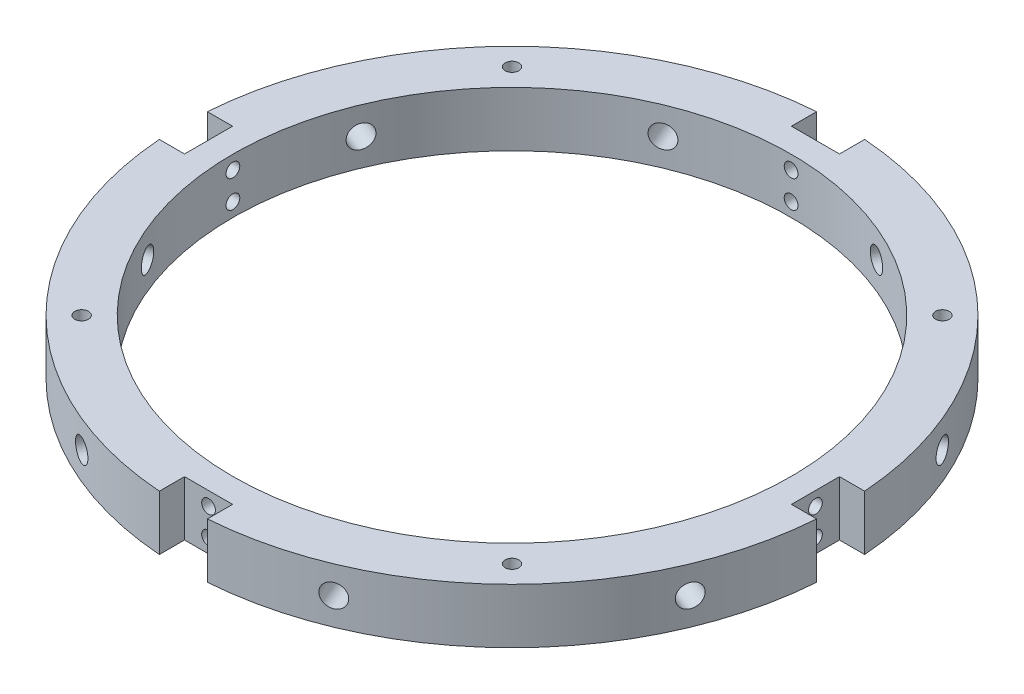
SolidWorks part; units mm, degrees
ref_plane "Front Plane" through (0, 0, 0) normal (0, 0, 1) x (1, 0, 0)
ref_plane "Top Plane" through (0, 0, 0) normal (0, 1, 0) x (1, 0, 0)
ref_plane "Right Plane" through (0, 0, 0) normal (1, 0, 0) x (0, 0, -1)
sketch "Sketch1" plane through (0, 0, 0) normal (0, 1, 0) x (1, 0, 0)
  circle A0 centre (0, 0) radius 72
  circle A1 centre (0, 0) radius 61
  dimension "OuterDiameter" = 144
  dimension "InnerDiameter" = 122
extrude "Boss-Extrude1" add sketch "Sketch1" along normal blind 6 and the other way blind 6
sketch "Sketch13" plane through (0, 6, 0) normal (0, 1, 0) x (1, 0, 0)
  line L0 (0, -87.0356) -> (0, 86.4553) construction
  line L1 (-98.9563, 0) -> (122.4152, 0) construction
  line L2 (0, 0) -> (106.0387, 106.0387) construction
  line L3 (-5.25, -62.375) -> (5.25, -62.375)
  line L4 (-5.25, -62.375) -> (-5.25, -60.7737)
  line L5 (-5.25, -60.7737) -> (5.25, -60.7737)
  line L6 (5.25, -62.375) -> (5.25, -60.7737)
  line L7 (-5.25, -62.375) -> (5.25, -60.7737) construction
  line L8 (-5.25, -60.7737) -> (5.25, -62.375) construction
  line L9 (-5.25, 60.7737) -> (5.25, 60.7737)
  line L10 (5.25, 62.375) -> (5.25, 60.7737)
  line L11 (-5.25, 62.375) -> (5.25, 62.375)
  line L12 (-5.25, 62.375) -> (-5.25, 60.7737)
  line L13 (-60.7737, -5.25) -> (-60.7737, 5.25)
  line L14 (-62.375, 5.25) -> (-60.7737, 5.25)
  line L15 (-62.375, -5.25) -> (-62.375, 5.25)
  line L16 (-62.375, -5.25) -> (-60.7737, -5.25)
  line L17 (62.375, -5.25) -> (60.7737, -5.25)
  line L18 (62.375, -5.25) -> (62.375, 5.25)
  line L19 (62.375, 5.25) -> (60.7737, 5.25)
  line L20 (60.7737, -5.25) -> (60.7737, 5.25)
  circle A0 centre (0, 0) radius 61 construction
  point P7 (0, -61.5743)
  dimension "D1" = 10.5
  dimension "D2" = 62.375
  dimension "D4" = 45
extrude "Boss-Extrude2" [suppressed] add sketch "Sketch13" against normal blind 12
sketch "Sketch5" plane through (0, 6, 0) normal (0, 1, 0) x (1, 0, 0)
  line L0 (0, 0) -> (53.7588, 53.7588) construction
  line L1 (0, 0) -> (47.0226, 47.0226) construction
  line L2 (-121.3123, 0) -> (150.1577, 0) construction
  circle A0 centre (47.0226, 47.0226) radius 1.5
  circle A1 centre (47.0226, -47.0226) radius 1.5
  circle A2 centre (-47.0226, -47.0226) radius 1.5
  circle A3 centre (-47.0226, 47.0226) radius 1.5
  dimension "MountingBoltDiameter" = 3
  dimension "D3" = 45
  dimension "D2" = 66.5
  dimension "D1" = 4
extrude "Cut-Extrude3" cut sketch "Sketch5" against normal through all
sketch "Sketch6" plane through (0, 6, 0) normal (0, 1, 0) x (1, 0, 0)
  line L0 (0, -83.4209) -> (0, 77.0416) construction
  line L1 (-88.8703, 0) -> (103.6253, 0) construction
  line L2 (-5.25, -66.3083) -> (5.25, -66.3083)
  line L4 (-5.25, 71.8083) -> (-5.25, 66.3083)
  line L5 (-5.25, 66.3083) -> (5.25, 66.3083)
  line L6 (5.25, 71.8083) -> (5.25, 66.3083)
  line L7 (-5.25, 71.8083) -> (5.25, 66.3083) construction
  line L8 (-5.25, 66.3083) -> (5.25, 71.8083) construction
  line L9 (5.25, -71.8083) -> (5.25, -66.3083)
  line L11 (-5.25, -71.8083) -> (-5.25, -66.3083)
  line L12 (0, 0) -> (60.635, 60.635) construction
  line L13 (66.3083, -5.25) -> (66.3083, 5.25)
  line L14 (71.8083, 5.25) -> (66.3083, 5.25)
  line L16 (71.8083, -5.25) -> (66.3083, -5.25)
  line L17 (-71.8083, -5.25) -> (-66.3083, -5.25)
  line L19 (-71.8083, 5.25) -> (-66.3083, 5.25)
  line L20 (-66.3083, -5.25) -> (-66.3083, 5.25)
  line L21 (71.8083, 5.25) -> (77.3083, 5.25)
  line L23 (-5.25, 71.8083) -> (-5.25, 77.3083)
  line L24 (-5.25, 77.3083) -> (5.25, 77.3083)
  line L25 (5.25, 71.8083) -> (5.25, 77.3083)
  line L27 (71.8083, -5.25) -> (77.3083, -5.25)
  line L28 (77.3083, 5.25) -> (77.3083, -5.25)
  line L29 (5.25, -71.8083) -> (5.25, -77.3083)
  line L31 (-5.25, -71.8083) -> (-5.25, -77.3083)
  line L32 (5.25, -77.3083) -> (-5.25, -77.3083)
  line L33 (-71.8083, -5.25) -> (-77.3083, -5.25)
  line L35 (-71.8083, 5.25) -> (-77.3083, 5.25)
  line L36 (-77.3083, -5.25) -> (-77.3083, 5.25)
  circle A0 centre (0, 0) radius 72 construction
  point P5 (0, 69.0583)
  point P43 (0, 0)
  circle M6 centre (0, 0) radius 72
  dimension "RailWidth" = 10.5
  dimension "D1" = 5.5
  dimension "D2" = 5.5
extrude "Cut-Extrude4" cut sketch "Sketch6" against normal through all contours L25 L24 L23 M6 | L6 L4 L5 | L28 L21 L27 M6 | L16 L14 L13 | L36 L33 L35 M6 | L17 L20 L19 | L32 L29 L31 M6 | L11 L9 L2 region at (0, 6, 69.1225) region at (0, 6, 74.6219) region at (-69.1225, 6, 0) region at (-74.6219, 6, 0) region at (74.6219, 6, 0) region at (69.1225, 6, 0) region at (0, 6, -69.1225) region at (0, 6, -74.6219)
sketch "Sketch12" plane through (0, 0, 66.3083) normal (0, 0, 1) x (1, 0, 0)
  line L0 (0, 14.272) -> (0, -15.4955) construction
  line L1 (-76.0318, 0) -> (77.9048, 0) construction
  circle A8 centre (0, 3) radius 1.5
  circle A9 centre (0, -3) radius 1.5
  dimension "D2" = 3
  dimension "D1" = 3
extrude "Cut-Extrude8" cut sketch "Sketch12" against normal through all
sketch "Sketch14" plane through (0, 6, 0) normal (0, 1, 0) x (1, 0, 0)
  line L0 (0, 0) -> (-136.7554, 0) construction
  line L1 (0, 0) -> (0, 142.5403) construction
  line L2 (0, 0) -> (-49.7797, 120.1788) construction
  line L3 (0, 0) -> (-96.3261, 96.3261) construction
  line L4 (0, 0) -> (-120.1788, 49.7797) construction
  line L5 (0, 0) -> (-49.7797, -120.1788) construction
  line L6 (0, 0) -> (-120.1788, -49.7797) construction
  line L7 (0, 0) -> (49.7797, -120.1788) construction
  line L8 (0, 0) -> (120.1788, -49.7797) construction
  line L9 (0, 0) -> (120.1788, 49.7797) construction
  line L10 (0, 0) -> (49.7797, 120.1788) construction
  dimension "D1" = 22.5
ref_plane "Plane1" through (-49.7797, 6, -120.1788) normal (-0.3827, 0, -0.9239) x (-0.9239, 0, 0.3827)
ref_plane "Plane2" through (-120.1788, 6, -49.7797) normal (-0.9239, 0, -0.3827) x (-0.3827, 0, 0.9239)
ref_plane "Plane3" through (-120.1788, 6, 49.7797) normal (-0.9239, 0, 0.3827) x (0.3827, 0, 0.9239)
ref_plane "Plane4" through (-49.7797, 6, 120.1788) normal (-0.3827, 0, 0.9239) x (0.9239, 0, 0.3827)
sketch "Sketch15" plane through (-49.7797, 6, -120.1788) normal (-0.3827, 0, -0.9239) x (-0.9239, 0, 0.3827)
  line L0 (-120.7735, -6) -> (151.4229, -6) construction
  circle A0 centre (0, -6) radius 2.5
  dimension "D1" = 5
extrude "Cut-Extrude10" cut sketch "Sketch15" against normal through all
cosmetic thread "Cosmetic Thread1" parameters "D2"=6
cosmetic thread "Cosmetic Thread5" parameters "D2"=6
sketch "Sketch16" plane through (-120.1788, 6, -49.7797) normal (-0.9239, 0, -0.3827) x (-0.3827, 0, 0.9239)
  line L0 (-99.0113, -6) -> (114.7123, -6) construction
  circle A0 centre (0, -6) radius 2.5
  dimension "D1" = 5
extrude "Cut-Extrude11" cut sketch "Sketch16" against normal through all
cosmetic thread "Cosmetic Thread2" parameters "D2"=6
cosmetic thread "Cosmetic Thread6" parameters "D2"=6
sketch "Sketch17" plane through (-120.1788, 6, 49.7797) normal (-0.9239, 0, 0.3827) x (0.3827, 0, 0.9239)
  line L0 (-104.6958, -6) -> (121.5008, -6) construction
  circle A0 centre (0, -6) radius 2.5
  dimension "D1" = 5
extrude "Cut-Extrude12" cut sketch "Sketch17" against normal through all
cosmetic thread "Cosmetic Thread3" parameters "D2"=6
cosmetic thread "Cosmetic Thread7" parameters "D2"=6
sketch "Sketch18" plane through (-49.7797, 6, 120.1788) normal (-0.3827, 0, 0.9239) x (0.9239, 0, 0.3827)
  line L0 (-104.7035, -6) -> (121.0277, -6) construction
  circle A0 centre (0, -6) radius 2.5
  dimension "D1" = 5
extrude "Cut-Extrude13" cut sketch "Sketch18" against normal through all
cosmetic thread "Cosmetic Thread4" parameters "D2"=6
cosmetic thread "Cosmetic Thread8" parameters "D2"=6
sketch "Sketch19" plane through (66.3083, 0, 0) normal (1, 0, 0) x (0, 0, -1)
  line L0 (0, 13.2441) -> (0, -16.5234) construction
  line L1 (-73.8627, 0) -> (80.0739, 0) construction
  line L2 (5.25, 6) -> (-5.25, 6) construction
  line L4 (-5.25, -6) -> (-5.25, 6) construction
  circle A1 centre (0, 3) radius 1.5
  circle A4 centre (0, -3) radius 1.5
  dimension "D2" = 3
  dimension "D13" = 6
  dimension "D3" = 3
  dimension "D4" = 5.25
extrude "Cut-Extrude14" cut sketch "Sketch19" against normal through all
equation "\"InternalDiameter\"= 122mm"
equation "\"ExternalDiameter\"= 144mm"
equation "\"InnerDiameter@Sketch1\"= \"InternalDiameter\""
equation "\"OuterDiameter@Sketch1\"= \"ExternalDiameter\""
equation "\"MountingBoltDiameter\"= 3mm"
equation "\"NumberOfMountingBolts\"= 4"
equation "\"MountingBoltDiameter@Sketch5\"= \"MountingBoltDiameter\""
equation "\"D1@Sketch5\"= \"NumberOfMountingBolts\""
equation "\"RailBoltDiameter\"= 6mm"
equation "\"RailBoltSpacing\"= 12mm"
equation "\"RailWidth\" = 10.5mm"
equation "\"RailWidth@Sketch6\" = \"RailWidth\""
equation "\"D1@Sketch13\" = \"RailWidth\""
equation "\"RailDepth\"= 5.5mm"
equation "\"D2@Sketch13\"= \"InternalDiameter\" / 2 + \"RailDepth\" / 4"
equation "\"TubeBoltAngularOffset\"= 22.5"
equation "\"D1@Sketch14\"= \"TubeBoltAngularOffset\""
equation "\"TubeBoltDiameter\"= 5mm"
equation "\"D1@Sketch16\"= \"TubeBoltDiameter\""
equation "\"D1@Sketch15\"= \"TubeBoltDiameter\""
equation "\"D1@Sketch17\"= \"TubeBoltDiameter\""
equation "\"D1@Sketch18\"= \"TubeBoltDiameter\""
equation "\"D13@Sketch19\"= 6mm"
equation "\"D1@Sketch12\"= \"MountingBoltDiameter@Sketch5\""
equation "\"D2@Sketch6\"= \"RailDepth\""
equation "\"D1@Sketch6\"= \"RailDepth\""
equation "\"D2@Sketch19\"= \"MountingBoltDiameter\""
equation "\"D4@Sketch19\"= \"RailWidth\" / 2"
